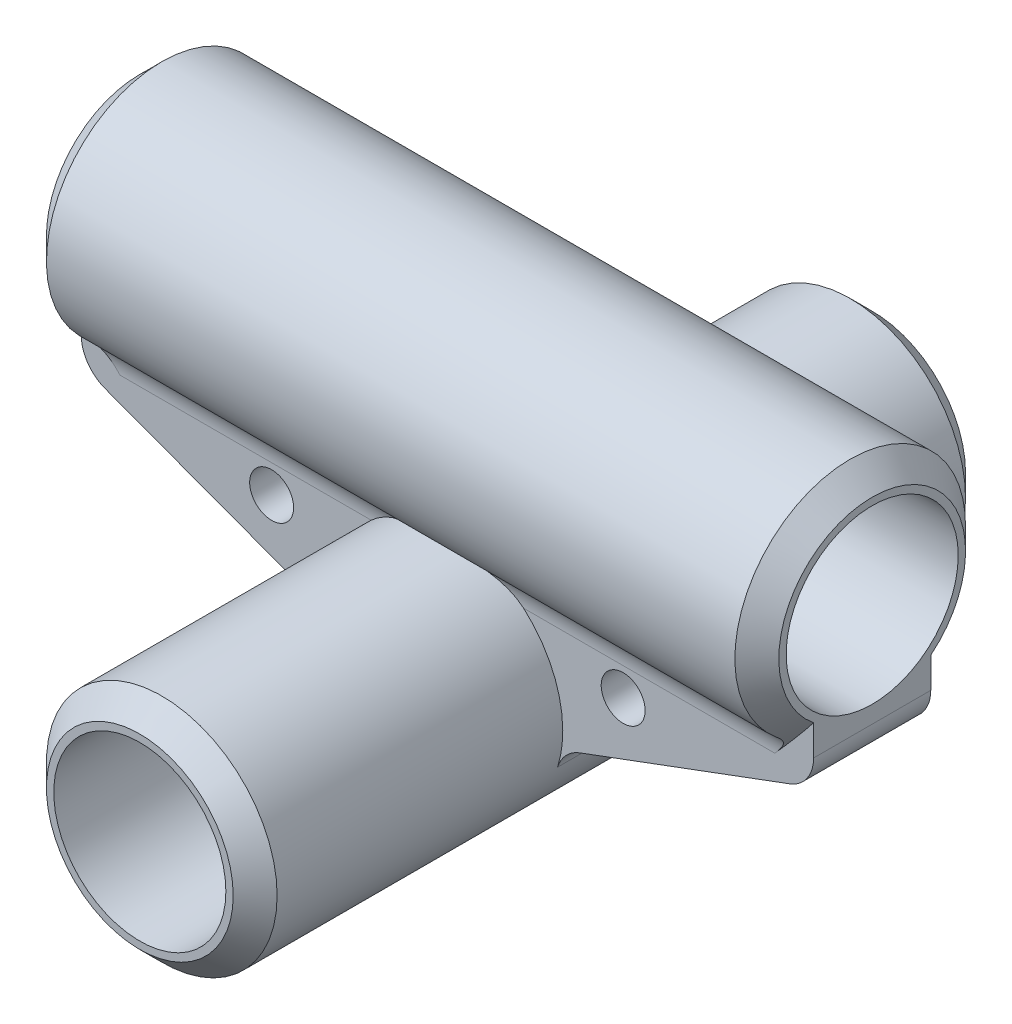
SolidWorks part; units mm, degrees
ref_plane "Plan de face" through (0, 0, 0) normal (0, 0, 1) x (1, 0, 0)
ref_plane "Plan de dessus" through (0, 0, 0) normal (0, 1, 0) x (1, 0, 0)
ref_plane "Plan de droite" through (0, 0, 0) normal (1, 0, 0) x (0, 0, -1)
sketch "Esquisse1" plane through (0, 0, 0) normal (0, 0, 1) x (1, 0, 0)
  circle A0 centre (0, 0) radius 11.75
  circle A1 centre (0, 0) radius 15.75
  dimension "D1" = 23.5
  dimension "D2" = 4
extrude "Boss.-Extru.1" add sketch "Esquisse1" along normal blind 100
sketch "Esquisse2" plane through (0, 0, 0) normal (1, 0, 0) x (0, 0, -1)
  line L0 (0, 0) -> (-100, 0) construction
  line L1 (-100, 15.75) -> (-100, -15.75) construction
  line L2 (-50, 0) -> (-50, 28) construction
  circle A0 centre (-50, 28) radius 11.75
  circle A1 centre (-50, 28) radius 15.75
  dimension "D1" = 23.5
  dimension "D2" = 4
  dimension "D3" = 28
extrude "Boss.-Extru.2" add sketch "Esquisse2" along normal blind 50 and the other way blind 50
sketch "Esquisse5" plane through (-50, 0, 0) normal (-1, 0, 0) x (0, 0, 1)
  line L0 (50, 16.25) -> (50, -15.75) construction
  line L1 (58, 15.75) -> (42, 15.75)
  line L2 (42, 15.75) -> (42, -15.75)
  line L3 (0, -15.75) -> (100, -15.75) construction
  line L4 (42, -15.75) -> (58, -15.75)
  line L5 (40.1006, 15.75) -> (0, 15.75) construction
  line L6 (58, 15.75) -> (58, -15.75)
  circle A0 centre (50, 28) radius 11.75 construction
  point P14 (50, 15.75)
  dimension "D1" = 16
extrude "Boss.-Extru.7" add sketch "Esquisse5" against normal up to surface (50 mm away) up to face at (2.7317, 15.5113, 40.4034)
extrude "Boss.-Extru.8" add sketch "Esquisse5<2>" along normal up to surface (50 mm away) from surface up to face at (-10.1824, -2.4843, 50.0834) starting at face at (50, 28, 34.25)
sketch "Esquisse5<2>" plane through (-50, 0, 0) normal (-1, 0, 0) x (0, 0, 1) same geometry as "Esquisse5"
sketch "Esquisse6" plane through (0, 0, 58) normal (0, 0, 1) x (1, 0, 0)
  line L2 (-50, -15.75) -> (-50, 10.433)
  line L3 (-50, -15.75) -> (-50, 14.433) construction
  line L4 (-50, 10.433) -> (-15.5695, -2.3777)
  line L5 (-6.3048, 14.433) -> (-50, 14.433) construction
  line L6 (0, 0) -> (0, 14.433) construction
  line L7 (50, 10.433) -> (15.5695, -2.3777)
  line L8 (50, -15.75) -> (50, 10.433)
  line L9 (-50, -15.75) -> (-50, -20.75)
  line L10 (-50, -20.75) -> (50, -20.75)
  line L11 (50, -20.75) -> (50, -15.75)
  line L12 (0, -15.75) -> (-50, -15.75) construction
  arc A0 (-15.5695, -2.3777) -> (15.5695, -2.3777) centre (0, 0) ccw
  circle A1 centre (0, 0) radius 15.75 construction
  arc A2 (-6.3048, 14.433) -> (0, -15.75) centre (0, 0) ccw construction
  point P22 (0, -15.75)
  point P24 (-50, 14.433)
  point P25 (-50, 11.3075)
  point P26 (-50, 10.433)
  point P27 (-15.5695, -2.3777)
  dimension "D2" = 5
  dimension "D3" = 4
extrude "Enlèv. mat.-Extru.1" cut sketch "Esquisse6" against normal through all both and the other way through all
fillet "Congé2" radius 5 4 edges at (50, 10.433, 50) (15.5695, -2.3777, 50) (-15.5695, -2.3777, 50) (-50, 10.433, 50)
chamfer "Chanfrein2" distance 3 angle 45 4 edges at (-50, 43.75, 50) (15.75, 0, 100) (50, 43.75, 50) (15.75, 0, 0)
sketch "Esquisse7" plane through (0, 0, 58) normal (0, 0, 1) x (1, 0, 0)
  line L0 (0, 0) -> (0, 9.9028) construction
  circle A0 centre (24, 8) radius 3
  circle A1 centre (-24, 8) radius 3
  dimension "D2" = 24
  dimension "D3" = 6
  dimension "D1" = 8
extrude "Enlèv. mat.-Extru.2" cut sketch "Esquisse7" against normal through all both and the other way through all
fillet "Congé3" radius 5 4 edges at (-26.6524, 14.433, 42) (26.6524, 14.433, 42) (26.6524, 14.433, 58) (-26.6524, 14.433, 58)
